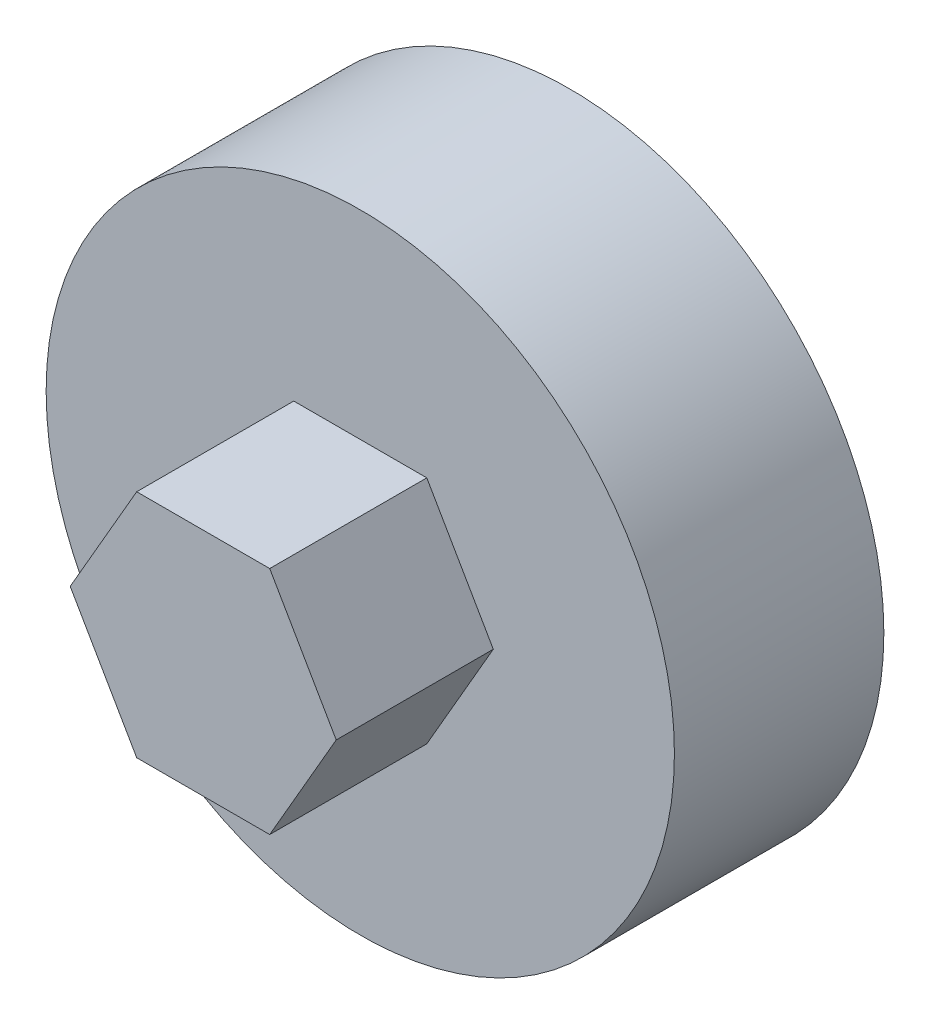
SolidWorks part; units mm, degrees
ref_plane "前视基准面" through (0, 0, 0) normal (0, 0, 1) x (1, 0, 0)
ref_plane "上视基准面" through (0, 0, 0) normal (0, 1, 0) x (1, 0, 0)
ref_plane "右视基准面" through (0, 0, 0) normal (1, 0, 0) x (0, 0, -1)
other "Configuration Table"
sketch "草图1" plane through (0, 0, 0) normal (0, 0, 1) x (1, 0, 0)
  line L0 (0, 0) -> (1.7387, 0.4659) construction
  line L1 (0, 0) -> (1.6291, 0.4551)
  line L2 (0, 0) -> (1.6291, -0.4551)
  line L3 (0, 0) -> (1.7387, -0.4659) construction
  line L4 (0, 0) -> (2.425, 0) construction
  line L5 (1.7387, 0.4659) -> (1.7387, -0.4659) construction
  circle A0 centre (0, 0) radius 1.525
  circle A1 centre (0, 0) radius 2.425
  circle A2 centre (0, 0) radius 1.6914 construction
  circle A3 centre (0, 0) radius 1.8 construction
  circle A4 centre (0, 0) radius 3
  spline S0 degree 4 poles (1.6291, 0.4551) (1.6415, 0.4586) (1.6769, 0.4656) (1.746, 0.4684) (1.8576, 0.4574) (1.9985, 0.4209) (2.171, 0.3489) (2.3582, 0.2351) (2.5438, 0.0819) (2.7191, -0.1093) (2.8693, -0.3205) (2.9946, -0.5472) (3.1006, -0.7975) (3.1986, -1.1195) (3.2658, -1.5159) (3.2754, -1.9832) (3.2064, -2.4974) (3.0631, -2.9965) (2.8558, -3.471) (2.5865, -3.9159) (2.2706, -4.3232) (1.901, -4.6937) (1.507, -5.0164) (1.0559, -5.3028) (0.6986, -5.4883) (0.2793, -5.6591) (0.0342, -5.7399) (-0.2484, -5.8241) (-0.3932, -5.8525) (-0.5197, -5.8826) (-0.5587, -5.8884) (-0.5863, -5.894) (-0.6011, -5.8971) knots 0 0 0 0 0 0.005604 0.015718 0.02996 0.048734 0.068727 0.096889 0.125051 0.153212 0.181374 0.209535 0.237696 0.271429 0.327752 0.384075 0.440398 0.496721 0.553044 0.609367 0.66569 0.722013 0.778336 0.834659 0.890982 0.909091 0.954545 0.977273 0.988636 0.994318 1 1 1 1 1 construction
  spline S1 degree 4 poles (1.6291, 0.4551) (1.6415, 0.4586) (1.6769, 0.4656) (1.746, 0.4684) (1.8576, 0.4574) (1.9985, 0.4209) (2.171, 0.3489) (2.3582, 0.2351) (2.5438, 0.0819) (2.7191, -0.1093) (2.8693, -0.3205) (2.9946, -0.5472) (3.1006, -0.7975) (3.1986, -1.1195) (3.2658, -1.5159) (3.2754, -1.9832) (3.2064, -2.4974) (3.0631, -2.9965) (2.8558, -3.471) (2.5865, -3.9159) (2.2706, -4.3232) (1.901, -4.6937) (1.507, -5.0164) (1.0559, -5.3028) (0.6986, -5.4883) (0.3874, -5.615) (0.2408, -5.6686) (0.2052, -5.6811) knots 0 0 0 0 0 0.005604 0.015718 0.02996 0.048734 0.068727 0.096889 0.125051 0.153212 0.181374 0.209535 0.237696 0.271429 0.327752 0.384075 0.440398 0.496721 0.553044 0.609367 0.66569 0.722013 0.778336 0.834659 0.890982 0.909091 0.909091 0.909091 0.909091 0.909091
  spline S2 degree 4 poles (1.6291, -0.4551) (1.6415, -0.4586) (1.6769, -0.4656) (1.746, -0.4684) (1.8576, -0.4574) (1.9985, -0.4209) (2.171, -0.3489) (2.3582, -0.2351) (2.5438, -0.0819) (2.7191, 0.1093) (2.8693, 0.3205) (2.9946, 0.5472) (3.1006, 0.7975) (3.1986, 1.1195) (3.2658, 1.5159) (3.2754, 1.9832) (3.2064, 2.4974) (3.0631, 2.9965) (2.8558, 3.471) (2.5865, 3.9159) (2.2706, 4.3232) (1.901, 4.6937) (1.507, 5.0164) (1.0559, 5.3028) (0.6986, 5.4883) (0.2793, 5.6591) (0.0342, 5.7399) (-0.2484, 5.8241) (-0.3932, 5.8525) (-0.5197, 5.8826) (-0.5587, 5.8884) (-0.5863, 5.894) (-0.6011, 5.8971) knots 0 0 0 0 0 0.005604 0.015718 0.02996 0.048734 0.068727 0.096889 0.125051 0.153212 0.181374 0.209535 0.237696 0.271429 0.327752 0.384075 0.440398 0.496721 0.553044 0.609367 0.66569 0.722013 0.778336 0.834659 0.890982 0.909091 0.954545 0.977273 0.988636 0.994318 1 1 1 1 1 construction
  spline S3 degree 4 poles (1.6291, -0.4551) (1.6415, -0.4586) (1.6769, -0.4656) (1.746, -0.4684) (1.8576, -0.4574) (1.9985, -0.4209) (2.171, -0.3489) (2.3582, -0.2351) (2.5438, -0.0819) (2.7191, 0.1093) (2.8693, 0.3205) (2.9946, 0.5472) (3.1006, 0.7975) (3.1986, 1.1195) (3.2658, 1.5159) (3.2754, 1.9832) (3.2064, 2.4974) (3.0631, 2.9965) (2.8558, 3.471) (2.5865, 3.9159) (2.2706, 4.3232) (1.901, 4.6937) (1.507, 5.0164) (1.0559, 5.3028) (0.6986, 5.4883) (0.3874, 5.615) (0.2408, 5.6686) (0.2052, 5.6811) knots 0 0 0 0 0 0.005604 0.015718 0.02996 0.048734 0.068727 0.096889 0.125051 0.153212 0.181374 0.209535 0.237696 0.271429 0.327752 0.384075 0.440398 0.496721 0.553044 0.609367 0.66569 0.722013 0.778336 0.834659 0.890982 0.909091 0.909091 0.909091 0.909091 0.909091
  point P16 (1.7387, 0)
  dimension "内啮合齿顶圆直径" = 3.05
  dimension "内啮合分度圆直径" = 3.6
  dimension "内啮合基圆直径" = 3.3829
  dimension "内啮合齿根圆直径" = 4.85
  dimension "外径" = 6
  dimension "渐开线镜像线夹角" = 15
extrude "凸台-拉伸1" add sketch "草图1" along normal blind 1 contours A4 | A0
extrude "切除-拉伸2" cut sketch "草图1<3>" along normal through all contours A0 S3 A1 S1 region at (1.9135, 0, 0)
sketch "草图1<3>" plane through (0, 0, 0) normal (0, 0, 1) x (1, 0, 0) same geometry as "草图1"
pattern_circular "阵列(圆周)1" count 9 over 360 about axis through (0, 0, 1) along (0, 0, 1) of "切除-拉伸2"
sketch "草图2" plane through (0, 0, 1) normal (0, 0, 1) x (1, 0, 0)
  line L1 (0.6351, 1.1) -> (-0.6351, 1.1)
  line L2 (-0.6351, 1.1) -> (-1.2702, 0)
  line L3 (-1.2702, 0) -> (-0.6351, -1.1)
  line L4 (-0.6351, -1.1) -> (0.6351, -1.1)
  line L5 (0.6351, -1.1) -> (1.2702, 0)
  line L6 (1.2702, 0) -> (0.6351, 1.1)
  circle A0 centre (0, 0) radius 3
  circle A1 centre (0, 0) radius 3 construction
  circle A2 centre (0, 0) radius 1.2702
  circle A3 centre (0, 0) radius 1.1 construction
  dimension "D1" = 2.2
extrude "凸台-拉伸2" add sketch "草图2" along normal blind 1 contours A0
extrude "凸台-拉伸3" add sketch "草图2<3>" along normal blind 1.5 from surface contours L1 L2 L3 L4 L5 L6 starting at face at (3, 0, 2)
sketch "草图2<3>" plane through (0, 0, 1) normal (0, 0, 1) x (1, 0, 0) same geometry as "草图2"
equation "\"m\"= 0.4'模数"
equation "\"z1\"= 6'外啮合齿轮数"
equation "\"a\"= 20度'压力角"
equation "\"z2\"= 9'内啮合齿轮数"
equation "\"hax\"= 1'齿顶高系数"
equation "\"cx\"= 0.25'顶隙系数"
equation "\"ha\"= \"hax\" * \"m\"'齿顶高"
equation "\"hf\"= ( \"hax\" + \"cx\" ) * \"m\"'齿根高"
equation "\"d1\"= \"m\" * \"z1\"'外啮合分度圆直径"
equation "\"da1\"= ( \"z1\" + 2 ) * \"m\"'外啮合齿顶圆直径"
equation "\"df1\"= \"d1\" - 2 * \"hf\"'外啮合齿根圆直径"
equation "\"db1\"= \"d1\" * cos ( \"a\" )'外啮合基圆直径"
equation "\"p\"= \"m\" * PI'齿距"
equation "\"d2\"= \"m\" * \"z2\"'内啮合分度圆直径"
equation "\"db2\"= \"d2\" * cos ( \"a\" )'内啮合基圆直径"
equation "\"da2\"= ( \"z2\" - 2 ) * \"m\"'内啮合齿顶圆直径"
equation "\"df2\"= \"d2\" + 2 * \"hf\"'内啮合齿根圆直径"
equation "\"内啮合齿顶圆直径@草图1\" = \"da2\" + 0.5 * \"hf\""
equation "\"内啮合齿根圆直径@草图1\"= \"df2\" + 0.5 * \"hf\""
equation "\"内啮合分度圆直径@草图1\"= \"d2\""
equation "\"内啮合基圆直径@草图1\"= \"db2\""
equation "\"渐开线镜像线夹角@草图1\"= 360度 / 4 / \"z2\" + 360度 / 4 / \"z2\" / 2"
equation "\"do\"= IIF ( \"edo\" >= ( \"df2\" + 1 ) , \"edo\" , ( \"df2\" + 1 ) )'外圈直径"
equation "\"h\"= 1'厚度"
equation "\"外径@草图1\"= \"do\""
equation "\"厚度@凸台-拉伸1\"= \"h\""
equation "\"内啮合齿轮数@阵列(圆周)1\"= \"z2\""
equation "\"edo\"= 6'期望的外圈直径"
